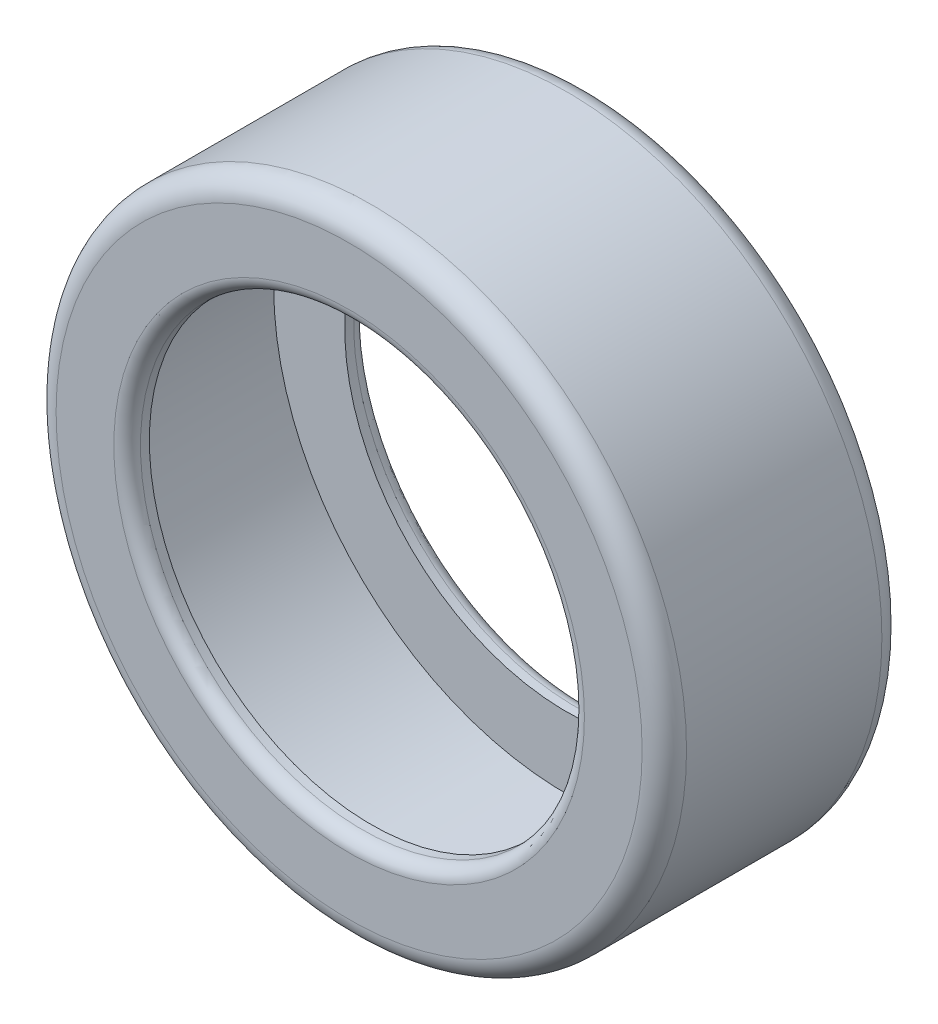
SolidWorks part; units mm, degrees
ref_plane "Front Plane" through (0, 0, 0) normal (0, 0, 1) x (1, 0, 0)
ref_plane "Top Plane" through (0, 0, 0) normal (0, 1, 0) x (1, 0, 0)
ref_plane "Right Plane" through (0, 0, 0) normal (1, 0, 0) x (0, 0, -1)
sketch "Sketch1" plane through (0, 0, 0) normal (0, 0, 1) x (1, 0, 0)
  circle A0 centre (0, 0) radius 50
  dimension "D1" = 100
extrude "Extrude-Thin1" add sketch "Sketch1" along normal blind 54 thin thin type one direction wall 21
fillet "Fillet1" radius 5 2 edges at (71, 0, 0) (71, 0, 54)
fillet "Fillet2" radius 3 2 edges at (50, 0, 0) (50, 0, 54)
shell "Shell2" thickness 5 removed face at (50, 0, 3)
